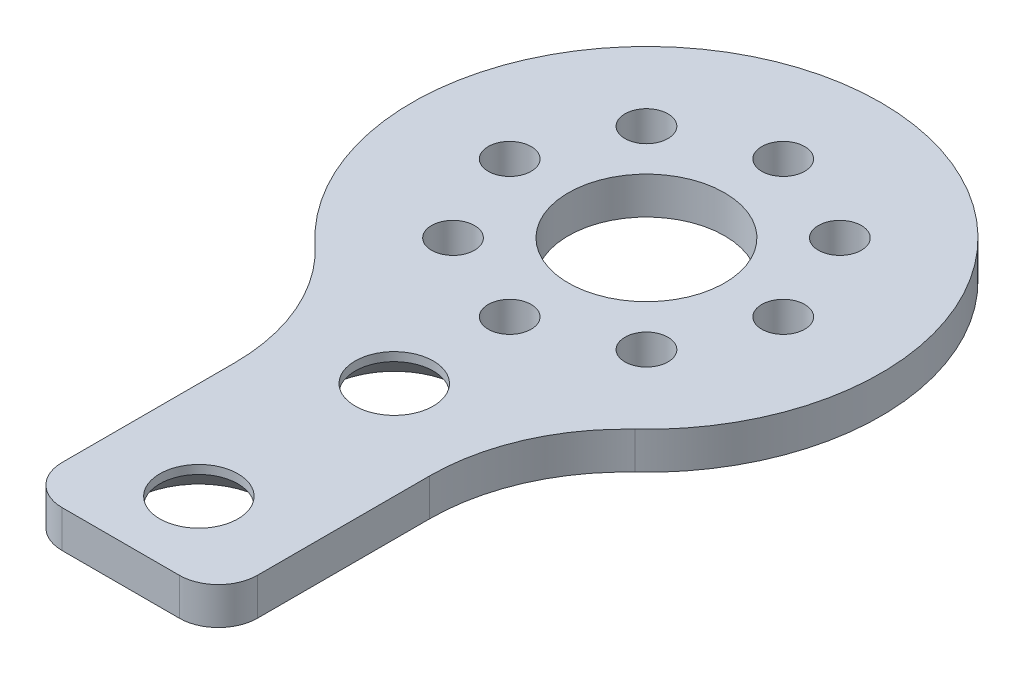
SolidWorks part; units mm, degrees
material "1060 Alloy"
ref_plane "Front Plane" through (0, 0, 0) normal (0, 0, 1) x (1, 0, 0)
ref_plane "Top Plane" through (0, 0, 0) normal (0, 1, 0) x (1, 0, 0)
ref_plane "Right Plane" through (0, 0, 0) normal (1, 0, 0) x (0, 0, -1)
sketch "Sketch1" plane through (0, 0, 0) normal (0, 1, 0) x (1, 0, 0)
  line L0 (-12.5, -67.2718) -> (12.5, -67.2718)
  line L1 (12.5, -67.2718) -> (12.5, -27.2718)
  line L2 (-12.5, -67.2718) -> (-12.5, -27.2718)
  arc A0 (12.5, -27.2718) -> (-12.5, -27.2718) centre (0, 0) ccw
  point P5 (0, -67.2718)
  dimension "D2" = 60
  dimension "D1" = 25
  dimension "D3" = 40
extrude "Boss-Extrude1" add sketch "Sketch1" along normal blind 4.7625 contours A0 L2 L0 L1
sketch "Sketch2" plane through (0, 0, 0) normal (0, -1, 0) x (1, 0, 0)
  circle A0 centre (0, 0) radius 17.5 construction
  point P3 (17.5, 0)
  point P6 (12.3744, -12.3744)
  point P7 (0, -17.5)
  point P8 (-12.3744, -12.3744)
  point P9 (-17.5, 0)
  point P10 (-12.3744, 12.3744)
  point P11 (0, 17.5)
  point P12 (12.3744, 12.3744)
  point P13 (0, 0)
  dimension "D2" = 35
  dimension "D1" = 8
hole_wizard "M5 Clearance Hole1" positions "Sketch3" profile "Sketch4" hole size "M5" standard "ANSI Metric" end condition through all
sketch "Sketch3" plane through (0, 0, 0) normal (0, -1, 0) x (-1, 0, 0)
  point P0 (0, 17.5)
  point P3 (12.3744, 12.3744)
  point P6 (17.5, 0)
  point P9 (12.3744, -12.3744)
  point P12 (0, -17.5)
  point P15 (-12.3744, -12.3744)
  point P18 (-17.5, 0)
  point P21 (-12.3744, 12.3744)
sketch "Sketch4" plane through (0, 0, -17.5) normal (1, 0, 0) x (0, 0, -1)
  line L0 (0, 0) -> (0, 4.7625)
  line L1 (0, 4.7625) -> (2.75, 4.7625)
  line L2 (2.75, 4.7625) -> (2.75, 0.025)
  line L3 (2.75, 0.025) -> (2.775, 0)
  line L5 (2.775, 0) -> (0, 0)
  line L6 (-2.75, 0.025) -> (-2.775, 0) construction
  line L11 (0, -6.35) -> (0, 107.95) construction
  dimension "Thru Hole Dia." = 5.5
  dimension "Thru Hole Depth" = 4.7625
  dimension "Near C'Sink Dia." = 5.55
  dimension "Near C'Sink Angle" = 90
sketch "Sketch5" plane through (0, 0, 0) normal (0, -1, 0) x (1, 0, 0)
  circle A0 centre (0, 0) radius 10
  dimension "D1" = 20
extrude "Cut-Extrude1" cut sketch "Sketch5" against normal through all
sketch "Sketch6" plane through (0, 0, 0) normal (0, -1, 0) x (1, 0, 0)
  line L0 (0, 67.2718) -> (0, 32.2718) construction
  line L1 (-12.5, 67.2718) -> (12.5, 67.2718) construction
  point P5 (0, 57.2718)
  dimension "D1" = 25
  dimension "D2" = 10
hole_wizard "CSK for M8 Flat Head Machine Screw1" positions "Sketch7" profile "Sketch8" countersink size "M8" standard "ANSI Metric" end condition through all
sketch "Sketch7" plane through (0, 0, 0) normal (0, -1, 0) x (-1, 0, 0)
  point P0 (0, -32.2718)
  point P3 (0, -57.2718)
sketch "Sketch8" plane through (0, 0, 32.2718) normal (1, 0, 0) x (0, 0, -1)
  line L0 (0, 0) -> (0, 4.7625)
  line L1 (0, 4.7625) -> (5, 4.7625)
  line L2 (5, 4.7625) -> (5, 3.65)
  line L3 (5, 3.65) -> (8.65, 0)
  line L5 (8.65, 0) -> (0, 0)
  line L6 (-5, 3.65) -> (-8.65, 0) construction
  line L11 (0, -6.35) -> (0, 107.95) construction
  dimension "Thru Hole Dia." = 10
  dimension "Thru Hole Depth" = 4.7625
  dimension "Near C'Sink Dia." = 17.3
  dimension "Near C'Sink Angle" = 90
fillet "Fillet1" radius 25 2 edges at (-12.5, 2.3813, 27.2718) (12.5, 2.3813, 27.2718)
fillet "Fillet2" radius 5 2 edges at (12.5, 2.3813, 67.2718) (-12.5, 2.3813, 67.2718)
